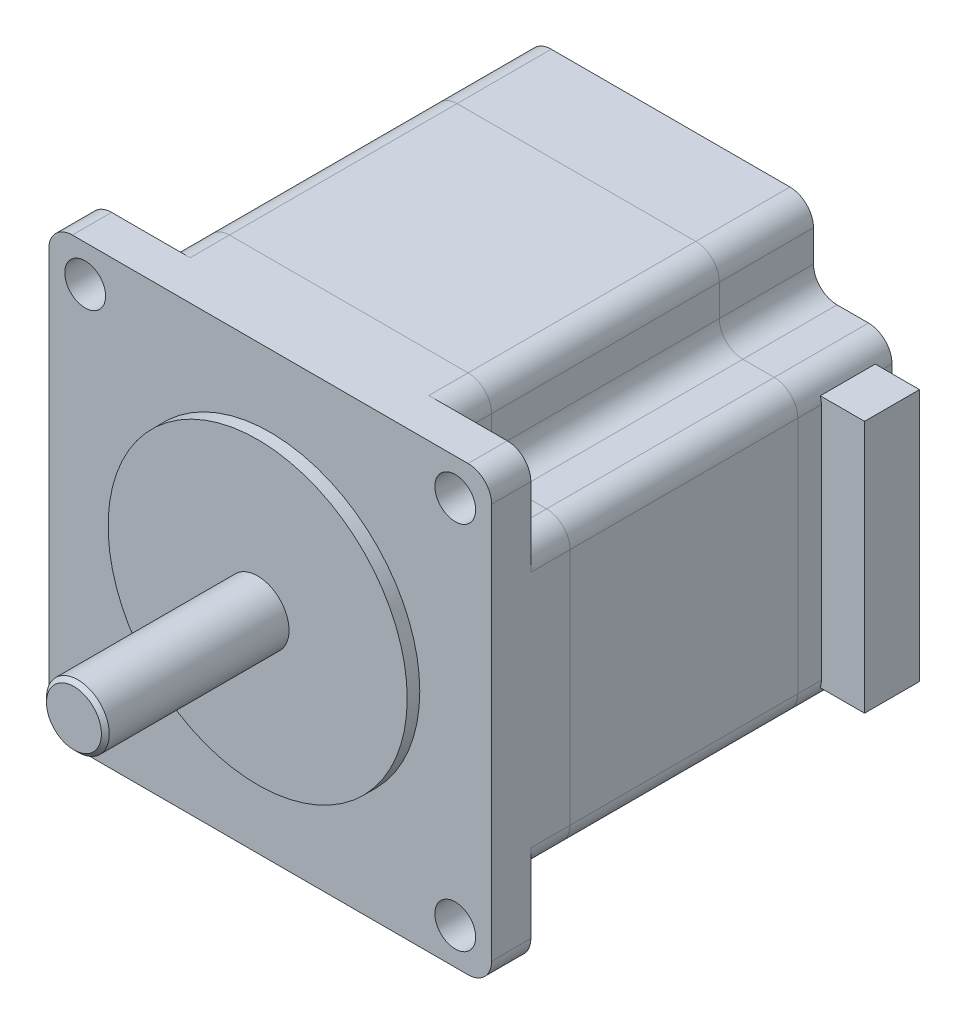
SolidWorks part; units mm, degrees
ref_plane "Front Plane" through (0, 0, 0) normal (0, 0, 1) x (1, 0, 0)
ref_plane "Top Plane" through (0, 0, 0) normal (0, 1, 0) x (1, 0, 0)
ref_plane "Right Plane" through (0, 0, 0) normal (1, 0, 0) x (0, 0, -1)
other "Configuration Table"
sketch "Sketch1" plane through (0, 0, 0) normal (0, 0, 1) x (1, 0, 0)
  line L1 (-28.2, 28.2) -> (28.2, 28.2)
  line L2 (-28.2, 28.2) -> (-28.2, -28.2)
  line L3 (-28.2, -28.2) -> (28.2, -28.2)
  line L4 (28.2, 28.2) -> (28.2, -28.2)
  line L5 (-28.2, 28.2) -> (28.2, -28.2) construction
  line L6 (-28.2, -28.2) -> (28.2, 28.2) construction
  point P0 (0, 0)
  dimension "D1" = 56.4
extrude "Boss-Extrude1" add sketch "Sketch1" against normal blind 5
sketch "Sketch2" plane through (0, 0, 0) normal (0, 0, 1) x (1, 0, 0)
  circle A0 centre (0, 0) radius 19.05
  dimension "D1" = 38.1
extrude "Boss-Extrude2" add sketch "Sketch2" along normal blind 1.6
sketch "Sketch3" plane through (0, 0, 1.6) normal (0, 0, 1) x (1, 0, 0)
  circle A0 centre (0, 0) radius 4
  dimension "ShalfDiameter" = 8
extrude "Shalf" add sketch "Sketch3" along normal blind 23.4
chamfer "Chamfer1" distance 0.5 angle 45 1 edges at (4, 0, 25)
sketch "Sketch4" plane through (0, 0, 0) normal (0, 0, 1) x (1, 0, 0)
  line L1 (-23.57, 23.57) -> (23.57, 23.57) construction
  line L2 (-23.57, 23.57) -> (-23.57, -23.57) construction
  line L3 (-23.57, -23.57) -> (23.57, -23.57) construction
  line L4 (23.57, 23.57) -> (23.57, -23.57) construction
  line L5 (-23.57, 23.57) -> (23.57, -23.57) construction
  line L6 (-23.57, -23.57) -> (23.57, 23.57) construction
  circle A0 centre (-23.57, 23.57) radius 2.6
  circle A1 centre (23.57, 23.57) radius 2.6
  circle A2 centre (-23.57, -23.57) radius 2.6
  circle A3 centre (23.57, -23.57) radius 2.6
  point P0 (0, 0)
  dimension "D1" = 5.2
  dimension "D2" = 47.14
extrude "Cut-Extrude1" cut sketch "Sketch4" against normal through all both and the other way through all
fillet "Fillet1" radius 3 4 edges at (28.2, -28.2, -2.5) (-28.2, -28.2, -2.5) (-28.2, 28.2, -2.5) (28.2, 28.2, -2.5)
sketch "Sketch5" plane through (0, 0, -5) normal (0, 0, -1) x (-1, 0, 0)
  line L0 (-25.2, 28.2) -> (25.2, 28.2) construction
  line L1 (-18.2, 28.2) -> (18.2, 28.2)
  line L2 (-28.2, 18.2) -> (-28.2, -18.2)
  line L5 (-28.2, -25.2) -> (-28.2, 25.2) construction
  line L8 (-28.2, 0) -> (28.2, 0) construction
  line L11 (-28.2, 18.2) -> (-18.2, 18.2)
  line L12 (-18.2, 28.2) -> (-18.2, 18.2)
  line L13 (0, 28.2) -> (0, -28.2) construction
  line L14 (18.2, 28.2) -> (18.2, 18.2)
  line L15 (28.2, 18.2) -> (18.2, 18.2)
  line L16 (28.2, 18.2) -> (28.2, -18.2)
  line L17 (-18.2, -28.2) -> (-18.2, -18.2)
  line L18 (-28.2, -18.2) -> (-18.2, -18.2)
  line L19 (28.2, -18.2) -> (18.2, -18.2)
  line L20 (18.2, -28.2) -> (18.2, -18.2)
  line L21 (-18.2, -28.2) -> (18.2, -28.2)
  dimension "D1" = 10
  dimension "D2" = 10
extrude "Boss-Extrude4" add sketch "Sketch5" along normal blind 46
fillet "Fillet2" radius 3 12 edges at (28.2, -18.2, -28) (18.2, -18.2, -28) (18.2, -28.2, -28) (-18.2, -28.2, -28) (-28.2, -18.2, -28) (-28.2, 18.2, -28) (-18.2, 28.2, -28) (28.2, 18.2, -28) (18.2, 28.2, -28) (-18.2, -18.2, -28) (-18.2, 18.2, -28) (18.2, 18.2, -28)
sketch "Sketch6" plane through (28.2, 0, 0) normal (1, 0, 0) x (0, 0, -1)
  line L0 (51, 0) -> (49, 0) construction
  line L1 (42, 16.1) -> (49, 16.1)
  line L2 (42, 16.1) -> (42, -16.1)
  line L3 (42, -16.1) -> (49, -16.1)
  line L4 (49, 16.1) -> (49, -16.1)
  line L5 (51, 15.2) -> (51, -15.2) construction
  dimension "D1" = 7
  dimension "D2" = 32.2
  dimension "D3" = 2
extrude "Boss-Extrude5" add sketch "Sketch6" along normal blind 5.5 and the other way blind 5
sketch "Sketch7" plane through (28.2, 0, 0) normal (1, 0, 0) x (0, 0, -1)
  line L0 (10, 28.2) -> (10, -28.2)
  line L1 (5, 28.2) -> (51, 28.2) construction
  line L2 (51, -28.2) -> (5, -28.2) construction
  line L3 (39, 28.2) -> (39, -28.2)
  line L4 (0, 19.05) -> (0, -19.05) construction
  line L5 (51, 15.2) -> (51, -15.2) construction
  dimension "D1" = 10
  dimension "D2" = 12
split line "Split Line3"
sketch "Sketch8" plane through (0, 0, 25) normal (0, 0, 1) x (1, 0, 0)
  line L0 (-3.4641, 2) -> (3.4641, 2)
  circle A0 centre (0, 0) radius 4 construction
  circle A1 centre (0, 0) radius 4 construction
  arc A2 (3.4641, 2) -> (-3.4641, 2) centre (0, 0) ccw
  arc A3 (-3.4641, 2) -> (3.4641, 2) centre (0, 0) ccw construction
  point P0 (0, -4)
  dimension "ShalfCutDiameter" = 6
extrude "Cut-Extrude2" [suppressed] cut sketch "Sketch8" against normal blind 20 and the other way through all
